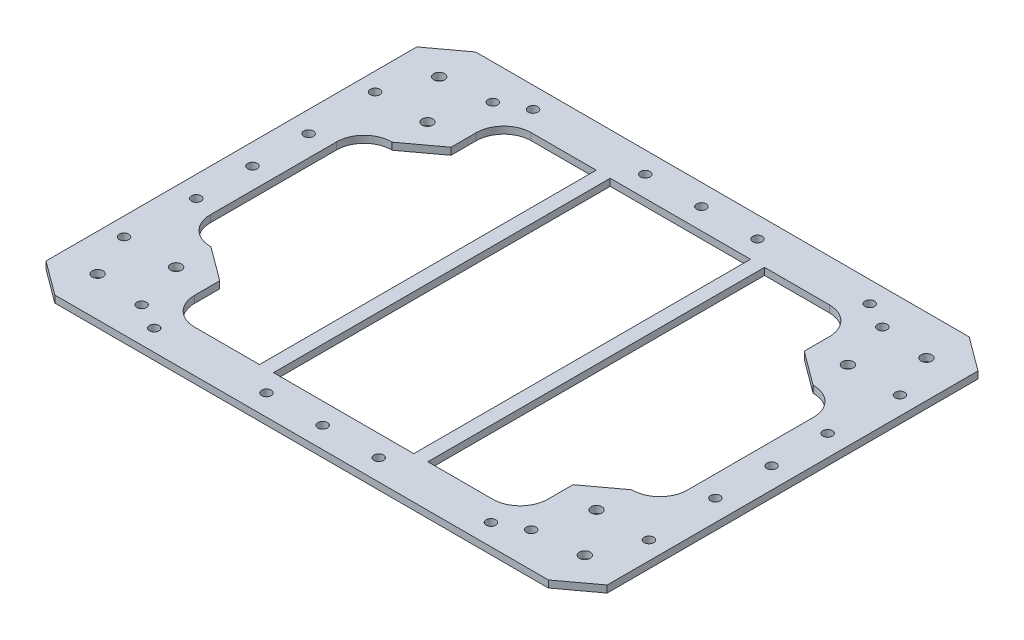
SolidWorks part; units mm, degrees
material "Thornel Mat VMA"
ref_plane "Front Plane" through (0, 0, 0) normal (0, 0, 1) x (1, 0, 0)
ref_plane "Top Plane" through (0, 0, 0) normal (0, 1, 0) x (1, 0, 0)
ref_plane "Right Plane" through (0, 0, 0) normal (1, 0, 0) x (0, 0, -1)
sketch "Sketch1" plane through (0, 0, 0) normal (0, 1, 0) x (1, 0, 0)
  line L0 (-127, 83.9186) -> (-111.6865, 95.25)
  line L1 (-127, -95.25) -> (127, -95.25)
  line L2 (-127, -95.25) -> (-127, 95.25)
  line L3 (-127, 95.25) -> (127, 95.25)
  line L4 (127, -95.25) -> (127, 95.25)
  line L5 (-107.95, 28.565) -> (-107.95, -28.565)
  line L7 (-38.1, -76.2) -> (-38.1, 76.2)
  line L8 (-95.504, 41.011) -> (-95.25, 41.011)
  line L9 (-31.75, -76.2) -> (-31.75, 76.2)
  line L10 (-127, 95.25) -> (127, -95.25) construction
  line L12 (127, 83.9186) -> (111.6865, 95.25)
  line L13 (38.1, -76.2) -> (38.1, 76.2)
  line L14 (79.9365, 52.3423) -> (79.9365, 63.754)
  line L15 (95.25, 41.011) -> (79.9365, 52.3423)
  line L16 (95.504, 41.011) -> (95.25, 41.011)
  line L17 (107.95, 28.565) -> (107.95, -28.565)
  line L18 (127, -83.9186) -> (111.6865, -95.25)
  line L19 (95.504, -41.011) -> (95.25, -41.011)
  line L20 (95.25, -41.011) -> (79.9365, -52.3423)
  line L21 (79.9365, -52.3423) -> (79.9365, -63.754)
  line L22 (127, 0) -> (-127, 0) construction
  line L23 (0, -13.6985) -> (0, 95.25) construction
  line L25 (-67.4905, -76.2) -> (-38.1, -76.2)
  line L26 (-79.9365, -52.3423) -> (-79.9365, -63.754)
  line L27 (-95.25, 41.011) -> (-127, 83.9186) construction
  line L28 (-95.25, 41.011) -> (-79.9365, 52.3423)
  line L29 (-79.9365, 52.3423) -> (-79.9365, 63.754)
  line L30 (-67.4905, 76.2) -> (-38.1, 76.2)
  line L31 (-95.25, -41.011) -> (-79.9365, -52.3423)
  line L32 (-95.504, -41.011) -> (-95.25, -41.011)
  line L33 (-127, -83.9186) -> (-111.6865, -95.25)
  line L34 (-79.9365, 52.3423) -> (-111.6865, 95.25) construction
  line L35 (31.75, -76.2) -> (31.75, 76.2)
  line L36 (-31.75, 76.2) -> (31.75, 76.2)
  line L37 (38.1, 76.2) -> (67.4905, 76.2)
  line L38 (-31.75, -76.2) -> (31.75, -76.2)
  line L39 (38.1, -76.2) -> (67.4905, -76.2)
  arc A0 (-79.9365, 63.754) -> (-67.4905, 76.2) centre (-67.4905, 63.754) cw
  arc A1 (79.9365, 63.754) -> (67.4905, 76.2) centre (67.4905, 63.754) ccw
  arc A2 (79.9365, -63.754) -> (67.4905, -76.2) centre (67.4905, -63.754) cw
  arc A3 (-67.4905, -76.2) -> (-79.9365, -63.754) centre (-67.4905, -63.754) cw
  arc A4 (-95.504, -41.011) -> (-107.95, -28.565) centre (-95.504, -28.565) cw
  arc A5 (-107.95, 28.565) -> (-95.504, 41.011) centre (-95.504, 28.565) cw
  arc A6 (95.504, 41.011) -> (107.95, 28.565) centre (95.504, 28.565) cw
  arc A7 (95.504, -41.011) -> (107.95, -28.565) centre (95.504, -28.565) ccw
  point P0 (0, 0)
  point P1 (0, 0)
  point P14 (0, 0)
  point P22 (0, 76.2)
  point P33 (107.95, 0)
  point P41 (0, 0)
  point P44 (-107.95, 0)
  point P45 (-38.1, 0)
  point P46 (-31.75, 0)
  dimension "D10" = 12.446
  dimension "D1" = 190.5
  dimension "D2" = 254
  dimension "D3" = 19.05
  dimension "D4" = 19.05
  dimension "D9" = 31.75
  dimension "D5" = 143.5
  dimension "D6" = 19.05
  dimension "D8" = 6.35
extrude "Boss-Extrude1" add sketch "Sketch1" along normal blind 3.175 contours L2 L1 L4 L3 L8 region at (-117.4547, 0, -87.0321)
sketch "Sketch2" plane through (0, 3.175, 0) normal (0, 1, 0) x (1, 0, 0)
  line L0 (-87.5933, 46.6767) -> (-119.3433, 89.5843) construction
  line L1 (-95.25, 41.011) -> (-79.9365, 52.3423) construction
  line L2 (-127, 83.9186) -> (-111.6865, 95.25) construction
  line L3 (0, 0) -> (0, 95.25) construction
  line L4 (-111.6865, 95.25) -> (111.6865, 95.25) construction
  line L5 (0, 0) -> (-127, 0) construction
  line L6 (-127, -83.9186) -> (-127, 83.9186) construction
  line L7 (-103.4683, 68.1305) -> (-88.1548, 79.4619) construction
  circle A0 centre (-95.1475, 56.8856) radius 2.4638
  circle A1 centre (-110.256, 77.3036) radius 2.4638
  circle A2 centre (110.256, 77.3036) radius 2.4638
  circle A3 centre (95.1475, 56.8856) radius 2.4638
  circle A4 centre (110.256, -77.3036) radius 2.4638
  circle A5 centre (95.1475, -56.8856) radius 2.4638
  circle A6 centre (-110.256, -77.3036) radius 2.4638
  circle A7 centre (-95.1475, -56.8856) radius 2.4638
  circle A8 centre (-88.1548, 79.4619) radius 2.159
  circle A9 centre (-118.7817, 56.7991) radius 2.159
  circle A10 centre (118.7817, 56.7991) radius 2.159
  circle A11 centre (88.1548, 79.4619) radius 2.159
  circle A12 centre (118.7817, -56.7991) radius 2.159
  circle A13 centre (88.1548, -79.4619) radius 2.159
  circle A14 centre (-88.1548, -79.4619) radius 2.159
  circle A15 centre (-118.7817, -56.7991) radius 2.159
  dimension "D2" = 4.9276
  dimension "D3" = 4.9276
  dimension "D5" = 4.318
  dimension "D1" = 25.4
  dimension "D4" = 12.7
  dimension "D6" = 19.05
extrude "Cut-Extrude1" cut sketch "Sketch2" against normal through all
sketch "Sketch3" plane through (0, 3.175, 0) normal (0, 1, 0) x (1, 0, 0)
  line L0 (-79.9365, 76.2) -> (-79.9365, 95.25) construction
  line L1 (-111.6865, 95.25) -> (111.6865, 95.25) construction
  line L2 (-79.9365, 85.725) -> (79.9365, 85.725) construction
  line L3 (79.9365, 76.2) -> (79.9365, 95.25) construction
  line L4 (0, 0) -> (76.2, 0) construction
  line L5 (-107.95, -41.011) -> (-127, -41.011) construction
  line L6 (-127, -83.9186) -> (-127, 83.9186) construction
  line L7 (-107.95, 41.011) -> (-127, 41.011) construction
  line L8 (-117.475, 41.011) -> (-117.475, -41.011) construction
  line L9 (0, 0) -> (0, 36.2879) construction
  circle A0 centre (-76.2, 85.725) radius 2.159
  circle A1 centre (-25.4, 85.725) radius 2.159
  circle A2 centre (25.4, 85.725) radius 2.159
  circle A3 centre (76.2, 85.725) radius 2.159
  circle A4 centre (76.2, -85.725) radius 2.159
  circle A5 centre (25.4, -85.725) radius 2.159
  circle A6 centre (-25.4, -85.725) radius 2.159
  circle A7 centre (-76.2, -85.725) radius 2.159
  circle A8 centre (-117.475, -25.4) radius 2.159
  circle A9 centre (-117.475, 25.4) radius 2.159
  circle A10 centre (117.475, 25.4) radius 2.159
  circle A11 centre (117.475, -25.4) radius 2.159
  circle A12 centre (0, 85.725) radius 2.159
  circle A13 centre (0, -85.725) radius 2.159
  circle A14 centre (-117.475, 0) radius 2.159
  circle A15 centre (117.475, 0) radius 2.159
  point P12 (0, 85.725)
  point P40 (-117.475, 0)
  dimension "D1" = 4.318
  dimension "D2" = 76.2
  dimension "D4" = 4.318
  dimension "D5" = 25.4
  dimension "D3" = 4
  dimension "D6" = 2
extrude "Cut-Extrude2" cut sketch "Sketch3" against normal through all
sketch "Sketch4" plane through (0, 3.175, 0) normal (0, 1, 0) x (1, 0, 0)
  line L0 (-95.1475, -56.8856) -> (-110.256, -74.8398) construction
